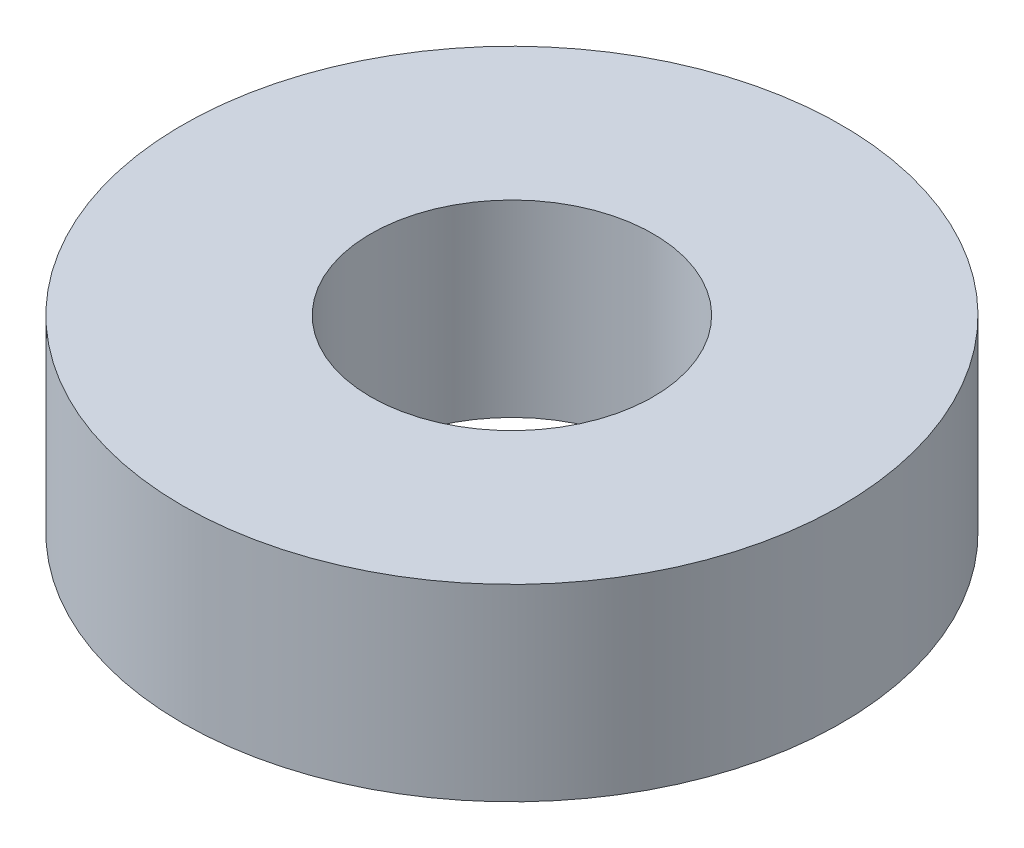
SolidWorks part; units mm, degrees
ref_plane "Front Plane" through (0, 0, 0) normal (0, 0, 1) x (1, 0, 0)
ref_plane "Top Plane" through (0, 0, 0) normal (0, 1, 0) x (1, 0, 0)
ref_plane "Right Plane" through (0, 0, 0) normal (1, 0, 0) x (0, 0, -1)
sketch "Sketch1" plane through (0, 0, 0) normal (0, 1, 0) x (1, 0, 0)
  circle A0 centre (0, 0) radius 52.5
  dimension "FLANGE_OD" = 105
extrude "Boss-Extrude1" add sketch "Sketch1" along normal blind 30
sketch "Sketch2" plane through (0, 0, 0) normal (0, 1, 0) x (1, 0, 0)
  circle A0 centre (0, 0) radius 22.5
  dimension "BORE_D" = 45
extrude "Cut-Extrude1" cut sketch "Sketch2" along normal through all
sketch "Sketch3" plane through (0, 30, 0) normal (0, 1, 0) x (1, 0, 0)
  circle A0 centre (0, 0) radius 14.1005 construction
  circle A1 centre (-14.1005, 0) radius 1.9523
  dimension "BOLT_D" = 3.9046
  dimension "BOLT_PCD" = 28.2011
extrude "Cut-Extrude2" cut sketch "Sketch3" against normal blind 18.311 rebuild error yes
pattern_circular "CirPattern1" count 4 over 360 rebuild error yes
